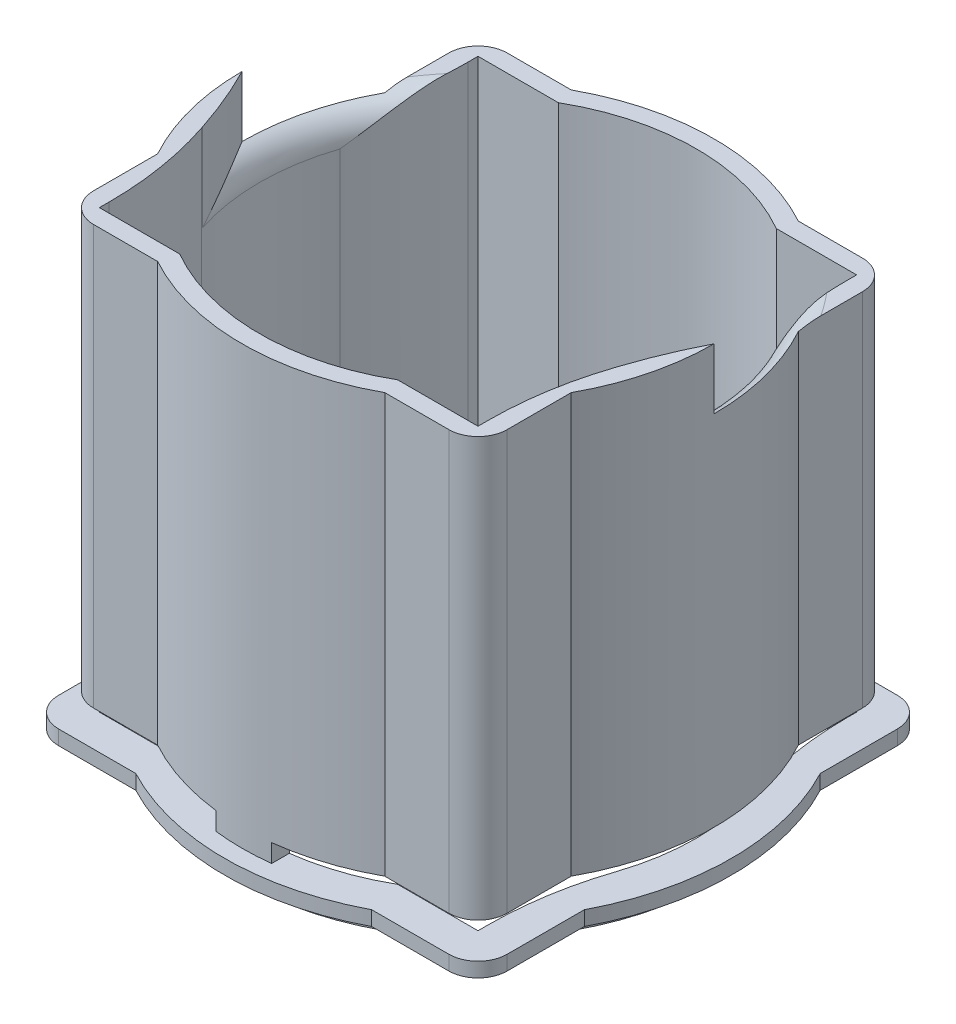
SolidWorks part; units mm, degrees
ref_plane "Front Plane" through (0, 0, 0) normal (0, 0, 1) x (1, 0, 0)
ref_plane "Top Plane" through (0, 0, 0) normal (0, 1, 0) x (1, 0, 0)
ref_plane "Right Plane" through (0, 0, 0) normal (1, 0, 0) x (0, 0, -1)
sketch "Sketch1" plane through (0, 0, 0) normal (0, 1, 0) x (1, 0, 0)
  line L0 (23.7595, 41.275) -> (41.275, 41.275)
  line L1 (-41.275, -41.275) -> (-23.7595, -41.275)
  line L2 (-41.275, -41.275) -> (-41.275, -23.7595)
  line L3 (-41.275, 41.275) -> (-23.7595, 41.275)
  line L4 (41.275, -41.275) -> (41.275, -23.7595)
  line L5 (-41.275, -41.275) -> (41.275, 41.275) construction
  line L6 (-41.275, 41.275) -> (41.275, -41.275) construction
  line L7 (41.275, 23.7595) -> (41.275, 41.275)
  line L8 (-41.275, 23.7595) -> (-41.275, 41.275)
  line L9 (23.7595, -41.275) -> (41.275, -41.275)
  line L10 (24.7569, 45.085) -> (45.085, 45.085)
  line L11 (45.085, 24.7569) -> (45.085, 45.085)
  line L12 (45.085, -45.085) -> (45.085, -24.7569)
  line L13 (24.7569, -45.085) -> (45.085, -45.085)
  line L14 (-45.085, -45.085) -> (-24.7569, -45.085)
  line L15 (-45.085, -45.085) -> (-45.085, -24.7569)
  line L16 (-45.085, 24.7569) -> (-45.085, 45.085)
  line L17 (-45.085, 45.085) -> (-24.7569, 45.085)
  arc A1 (-41.275, 23.7595) -> (-41.275, -23.7595) centre (0, 0) ccw
  arc A2 (23.7595, 41.275) -> (-23.7595, 41.275) centre (0, 0) ccw
  arc A3 (-23.7595, -41.275) -> (23.7595, -41.275) centre (0, 0) ccw
  arc A4 (41.275, -23.7595) -> (41.275, 23.7595) centre (0, 0) ccw
  arc A5 (45.085, -24.7569) -> (45.085, 24.7569) centre (0, 0) ccw
  arc A6 (-24.7569, -45.085) -> (24.7569, -45.085) centre (0, 0) ccw
  arc A7 (-45.085, 24.7569) -> (-45.085, -24.7569) centre (0, 0) ccw
  arc A8 (24.7569, 45.085) -> (-24.7569, 45.085) centre (0, 0) ccw
  point P0 (0, 0)
  dimension "D1" = 82.55
  dimension "D2" = 82.55
  dimension "D3" = 95.25
  dimension "D4" = 3.81
extrude "Boss-Extrude1" add sketch "Sketch1" along normal blind 101.6
sketch "Sketch6" plane through (0, 0, 0) normal (0, 0, 1) x (1, 0, 0)
  line L1 (-56.642, 10.287) -> (-6.096, 10.287)
  line L2 (-56.642, 10.287) -> (-56.642, 6.35)
  line L3 (-56.642, 6.35) -> (-6.096, 6.35)
  line L5 (-45.085, 0) -> (-24.7569, 0) construction
  line L8 (-6.096, 10.287) -> (-6.096, 6.35)
  line L9 (0, 0) -> (0, 21.9448) construction
  line L10 (6.096, 10.287) -> (6.096, 6.35)
  line L11 (56.642, 6.35) -> (6.096, 6.35)
  line L12 (56.642, 10.287) -> (6.096, 10.287)
  line L13 (56.642, 10.287) -> (56.642, 6.35)
  dimension "D3" = 3.937
  dimension "D1" = 6.096
  dimension "D4" = 6.35
extrude "Cut-Extrude4" cut sketch "Sketch6" against normal through all both and the other way through all
ref_plane "Plane1" through (0, 69.85, 0) normal (0, 1, 0) x (1, 0, 0)
sketch "Sketch12" plane through (0, 101.6, 0) normal (0, -1, 0) x (1, 0, 0)
  line L0 (25.7155, -48.895) -> (48.895, -48.895)
  line L1 (48.895, -48.895) -> (48.895, -25.7155)
  line L2 (48.895, 25.7155) -> (48.895, 48.895)
  line L3 (48.895, 48.895) -> (25.7155, 48.895)
  line L4 (-25.7155, 48.895) -> (-48.895, 48.895)
  line L5 (-48.895, 48.895) -> (-48.895, 25.7155)
  line L6 (-48.895, -25.7155) -> (-48.895, -48.895)
  line L7 (-48.895, -48.895) -> (-25.7155, -48.895)
  line L8 (24.7569, -45.085) -> (45.085, -45.085)
  line L9 (45.085, -45.085) -> (45.085, -24.7569)
  line L10 (45.085, 24.7569) -> (45.085, 45.085)
  line L11 (45.085, 45.085) -> (24.7569, 45.085)
  line L12 (-24.7569, 45.085) -> (-45.085, 45.085)
  line L13 (-45.085, 45.085) -> (-45.085, 24.7569)
  line L14 (-45.085, -24.7569) -> (-45.085, -45.085)
  line L15 (-45.085, -45.085) -> (-24.7569, -45.085)
  line L16 (24.7569, -45.085) -> (45.085, -45.085)
  line L17 (45.085, -45.085) -> (45.085, -24.7569)
  line L18 (45.085, 24.7569) -> (45.085, 45.085)
  line L19 (45.085, 45.085) -> (24.7569, 45.085)
  line L20 (-24.7569, 45.085) -> (-45.085, 45.085)
  line L21 (-45.085, 45.085) -> (-45.085, 24.7569)
  line L22 (-45.085, -24.7569) -> (-45.085, -45.085)
  line L23 (-45.085, -45.085) -> (-24.7569, -45.085)
  arc A0 (48.895, -25.7155) -> (48.895, 25.7155) centre (0, 0) ccw
  arc A3 (25.7155, 48.895) -> (-25.7155, 48.895) centre (0, 0) ccw
  arc A4 (-48.895, 25.7155) -> (-48.895, -25.7155) centre (0, 0) ccw
  arc A5 (-25.7155, -48.895) -> (25.7155, -48.895) centre (0, 0) ccw
  arc A7 (-24.7569, -45.085) -> (24.7569, -45.085) centre (0, 0) ccw
  arc A8 (45.085, -24.7569) -> (45.085, 24.7569) centre (0, 0) ccw
  arc A9 (24.7569, 45.085) -> (-24.7569, 45.085) centre (0, 0) ccw
  arc A10 (-45.085, 24.7569) -> (-45.085, -24.7569) centre (0, 0) ccw
  arc A11 (-24.7569, -45.085) -> (24.7569, -45.085) centre (0, 0) ccw
  arc A12 (45.085, -24.7569) -> (45.085, 24.7569) centre (0, 0) ccw
  arc A13 (24.7569, 45.085) -> (-24.7569, 45.085) centre (0, 0) ccw
  arc A14 (-45.085, 24.7569) -> (-45.085, -24.7569) centre (0, 0) ccw
  dimension "D1" = 0
  dimension "D2" = 3.81
extrude "Boss-Extrude9" add sketch "Sketch12" along normal blind 3.175 from surface at 95.25 starting at face at (-30.0451, 6.35, 0)
sketch "Sketch13" plane through (0, 0, 0) normal (0, 0, 1) x (1, 0, 0)
  line L0 (24.7569, 101.6) -> (-24.7569, 101.6) construction
  line L1 (-51.435, 101.6) -> (51.435, 101.6)
  line L2 (-51.435, 101.6) -> (-51.435, 88.9)
  line L3 (-51.435, 88.9) -> (51.435, 88.9)
  line L4 (51.435, 101.6) -> (51.435, 88.9)
  line L9 (-45.085, 101.6) -> (-51.435, 101.6) construction
  line L10 (51.435, 101.6) -> (45.085, 101.6) construction
  dimension "D1" = 12.7
extrude "Cut-Extrude6" cut sketch "Sketch13" against normal through all
fillet "Fillet1" radius 76.2 8 edges at (41.275, 55.9435, 23.7595) (-41.275, 55.9435, 23.7595) (-41.275, 3.175, -23.7595) (-41.275, 3.175, 23.7595) (41.275, 3.175, 23.7595) (41.275, 3.175, -23.7595) (-41.275, 49.5935, -23.7595) (41.275, 49.5935, -23.7595)
fillet "Fillet2" radius 101.6 2 edges at (-47.625, 95.25, 0) (47.625, 95.25, 0)
fillet "Fillet5" radius 6.35 2 edges at (-47.6248, 88.9, -0.1363) (47.6248, 88.9, -0.1363)
fillet "Fillet6" radius 6.35 12 edges at (45.085, 1.5875, 45.085) (48.895, 4.7625, 48.895) (45.085, 1.5875, -45.085) (48.895, 4.7625, -48.895) (-45.085, 1.5875, -45.085) (-48.895, 4.7625, -48.895) (-45.085, 1.5875, 45.085) (-48.895, 4.7625, 48.895) (-45.085, 49.5935, -45.085) (45.085, 49.5935, -45.085) (45.085, 55.9435, 45.085) (-45.085, 55.9435, 45.085)
equation "\"tightTol\" = 0.005in"
equation "\"normTol\"= 0.01in"
equation "\"looseTol\"= 0.02in"
equation "\"D1@Sketch6\" = 0.250000in - \"normTol\""
equation "\"D3@Sketch6\"=1.5*\"looseTol\"+0.125000in"
